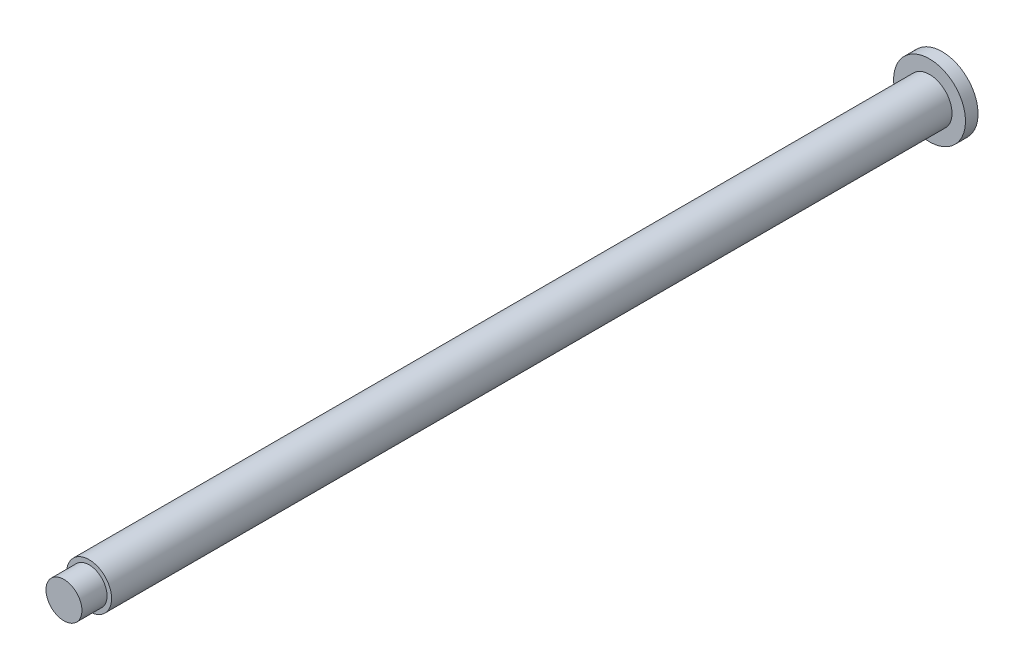
SolidWorks part; units mm, degrees
ref_plane "Front Plane" through (0, 0, 0) normal (1, 0, 0) x (0, 1, 0)
ref_plane "Top Plane" through (0, 0, 0) normal (0, 0, 1) x (0, 1, 0)
ref_plane "Right Plane" through (0, 0, 0) normal (0, 1, 0) x (-1, 0, 0)
sketch "Sketch1" plane through (0, 0, 0) normal (0, 0, 1) x (0, 1, 0)
  circle A0 centre (0, 0) radius 2.5
  dimension "D1" = 5
extrude "Boss-Extrude1" add sketch "Sketch1" along normal blind 93.5 contours A0
sketch "Sketch2" plane through (0, 0, 0) normal (0, 0, -1) x (1, 0, 0)
  circle A0 centre (0, 0) radius 4
  dimension "D1" = 8
extrude "Boss-Extrude2" add sketch "Sketch2" along normal blind 1.4
sketch "Sketch3" plane through (0, 0, -1.4) normal (0, 0, -1) x (1, 0, 0)
  circle A0 centre (0, 0) radius 2.05
  dimension "D1" = 4.1
extrude "Cut-Extrude1" cut sketch "Sketch3" against normal blind 3
sketch "Sketch4" plane through (0, 0, 93.5) normal (0, 0, 1) x (1, 0, 0)
  circle A0 centre (0, 0) radius 2
extrude "Boss-Extrude3" add sketch "Sketch4" along normal blind 2.8
equation "\"whitekey_cutout_length\"= 101.5"
equation "\"key_mount_recess_length\"=50"
equation "\"key_mount_recess_height\"=12.5"
equation "\"key_mount_recess_depth\"=1.5"
equation "\"wall_thickness\"=10"
equation "\"guide_brace_height\"=20"
equation "\"guide_brace_thickness\"=2"
equation "\"dowel_recess_depth\"=10"
equation "\"dowel_recess_offset\"=3.25"
equation "\"base_mount_height\"=40"
equation "\"base_rear_length\"=80"
equation "\"base_front_length\"=111.5"
equation "\"screw_hole_wall_offset\"=7.25"
equation "\"screw_hole_edge_inset\"=\"dowel_recess_depth\"/2"
equation "\"screw_hole_diameter\"=3.8"
equation "\"screw_head_hole_diameter\"=6.7"
equation "\"screw_nut_hole_side_len\"=3.5"
equation "\"screw_nut_recess_offset\"=0.35"
equation "\"screw_head_and_nut_recess_depth\"=2.5"
equation "\"screw_shaft_diameter\"=3.5"
equation "\"switch_board_width\"=30"
equation "\"switch_board_wall_offset\"=11.5"
equation "\"heatset_insert_hole_diameter\"=4.8"
equation "\"heatset_insert_hole_depth\"=3.8"
equation "\"front_rear_panel_width\"=23.75"
equation "\"rod_length_adj\"=0.5"
equation "\"rod_insert_length\"=2.8"
equation "\"D1@Boss-Extrude3\"=\"rod_insert_length\""
equation "\"D1@Boss-Extrude2\"=2-\"rod_length_adj\"-0.1"
equation "\"D1@Boss-Extrude1\"=\"rod_length_adj\"+93.00mm"
equation "\"switch_board_thickness\"=1.6"
equation "\"rod_diameter\"=5"
equation "\"rod_head_diameter\"=8"
equation "\"switch_black_key_mount_height\"=8"
equation "\"switch_white_key_mount_height\"=3"
equation "\"D1@Sketch1\"=\"rod_diameter\""
equation "\"D1@Sketch2\"=\"rod_head_diameter\""
equation "\"D1@Sketch3\"=\"rod_diameter\"-1+0.1"
equation "\"D1@Sketch4\"=\"rod_diameter\"-1"
